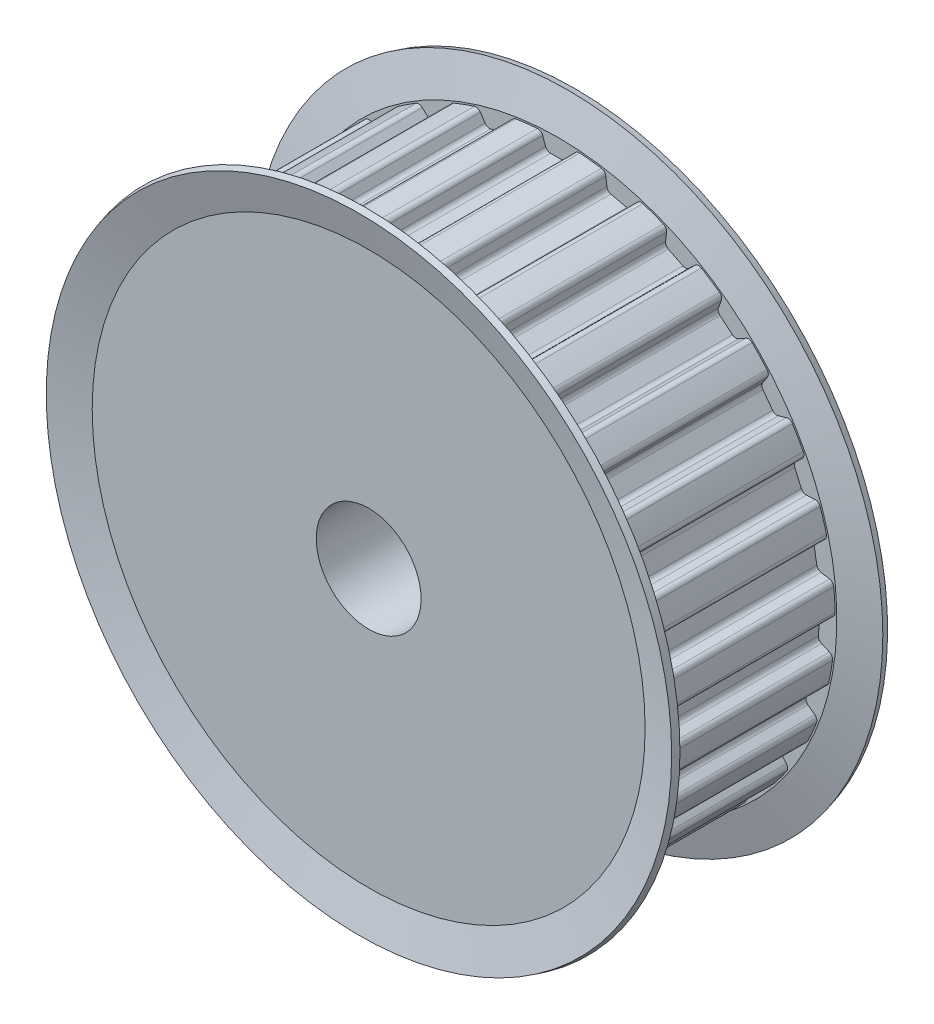
SolidWorks part; units mm, degrees
ref_plane "Front" through (0, 0, 0) normal (0, 0, 1) x (1, 0, 0)
ref_plane "Top" through (0, 0, 0) normal (0, 1, 0) x (1, 0, 0)
ref_plane "Right" through (0, 0, 0) normal (1, 0, 0) x (0, 0, -1)
sketch "support-front-body" plane through (0, 0, 0) normal (0, 0, 1) x (1, 0, 0)
  line L0 (0, 0) -> (0, 21.1) construction
  line L1 (0, 0) -> (0, -21.1) construction
  line L2 (0, 0) -> (21.1, 0) construction
  line L3 (0, 0) -> (-21.1, 0) construction
  circle A0 centre (0, 0) radius 21.1
  dimension "diam-outer" = 42.2
sketch "support-right-body" plane through (0, 0, 0) normal (1, 0, 0) x (0, 0, -1)
  line L0 (0, 0) -> (15, 0) construction
  line L1 (0, 21.1) -> (15, 21.1)
  line L2 (0, 21.1) -> (0, -21.1)
  line L3 (0, -21.1) -> (15, -21.1)
  line L4 (15, 21.1) -> (15, -21.1)
  dimension "width" = 15
sketch "support-right-hub" plane through (0, 0, 0) normal (1, 0, 0) x (0, 0, -1)
  line L0 (21, 0) -> (15, 0) construction
  line L1 (15, 15) -> (21, 15)
  line L2 (15, 15) -> (15, -15)
  line L3 (15, -15) -> (21, -15)
  line L4 (21, 15) -> (21, -15)
  line L5 (15, 21.1) -> (15, -21.1) construction
  line L6 (0, 0) -> (15, 0) construction
  line L8 (0, 21.1) -> (0, -21.1) construction
  dimension "diam-hub" = 30
  dimension "dist-hub" = 21
sketch "support-right-bore" plane through (0, 0, 0) normal (1, 0, 0) x (0, 0, -1)
  line L0 (0, 21.1) -> (0, -21.1) construction
  line L1 (0, 4) -> (21, 4)
  line L2 (0, 4) -> (0, -4)
  line L3 (0, -4) -> (21, -4)
  line L4 (21, 15) -> (21, -15) construction
  line L5 (21, 0) -> (0, 0) construction
  line L6 (0, 0) -> (15, 0) construction
  line L7 (21, 4) -> (21, -4)
  line L8 (21, -4) -> (21, 4) construction
  dimension "diam-bore" = 8
sketch "support-stop-screw-hole" plane through (0, 0, 0) normal (1, 0, 0) x (0, 0, -1)
  line L1 (6.5667, 11) -> (9.4333, 11)
  line L2 (6.5667, 11) -> (6.5667, -1)
  line L3 (8, -1) -> (9.4333, -1)
  line L4 (9.4333, 11) -> (9.4333, -1)
  line L5 (8, -1) -> (8, 11) construction
  line L6 (8, -1) -> (6.5667, -1)
  line L7 (0, 0) -> (8, 0) construction
  line L8 (0, 21.1) -> (0, -21.1) construction
  dimension "diam-stop-screw-hole" = 2.8665
  dimension "dist-stop-screw-hole" = 8
  dimension "depth-stop-screw-hole" = 12
  dimension "angle-stop-screw-hole" = 180
  dimension "height-stop-screw-hole" = 11
sketch "support-front-keygroove" plane through (0, 0, 0) normal (0, 0, 1) x (1, 0, 0)
  line L0 (0, 0) -> (0, -4) construction
  line L1 (-1, 4) -> (1, 4)
  line L2 (-1, 4) -> (-1, 1.8)
  line L3 (-1, 1.8) -> (1, 1.8)
  line L4 (1, 4) -> (1, 1.8)
  line L5 (0, 0) -> (0, 4) construction
  circle A0 centre (0, 0) radius 4 construction
  dimension "width-keygroove" = 2
  dimension "dist-keygroove" = 8
  dimension "height-keygroove" = 2.2
sketch "support-front-tooth" plane through (0, 0, 0) normal (0, 0, 1) x (1, 0, 0)
  line L0 (0, 0) -> (0, 22.2373) construction
  line L1 (-1.2186, 20.7753) -> (-0.9958, 20.1632)
  line L2 (-1.6253, 22.2373) -> (1.6253, 22.2373)
  line L3 (1.6253, 22.2373) -> (1.6253, 21.0373)
  line L4 (-1.6253, 22.2373) -> (-1.6253, 21.0373)
  line L5 (-2.5, 22.2373) -> (2.5, 22.2373) construction
  line L6 (1.6253, 21.0373) -> (2.5, 22.2373) construction
  line L7 (0, 21.1) -> (0, 19.9) construction
  line L8 (0, 21.1) -> (1.6253, 21.1) construction
  line L10 (-0.6199, 19.9) -> (0.6199, 19.9)
  line L11 (1.2186, 20.7753) -> (0.9958, 20.1632)
  line L12 (-0.9958, 20.1632) -> (-0.9, 19.9) construction
  line L13 (-0.9, 19.9) -> (-0.6199, 19.9) construction
  line L14 (0.9958, 20.1632) -> (0.9, 19.9) construction
  line L15 (0.9, 19.9) -> (0.6199, 19.9) construction
  circle A0 centre (0, 0) radius 21.1 construction
  arc A1 (-0.9958, 20.1632) -> (-0.6199, 19.9) centre (-0.6199, 20.3) ccw
  arc A3 (1.6253, 21.0373) -> (1.2186, 20.7753) centre (1.5945, 20.6385) ccw
  circle A4 centre (0, 0) radius 21.1 construction
  arc A5 (-1.6253, 21.0373) -> (-1.2186, 20.7753) centre (-1.5945, 20.6385) cw
  arc A6 (0.9958, 20.1632) -> (0.6199, 19.9) centre (0.6199, 20.3) cw
  point P26 (0, 19.9)
  dimension "rad-top" = 0.4
  dimension "rad-bottom" = 0.4
  dimension "height-tooth" = 1.2
  dimension "pitch" = 5
  dimension "angle" = 40
  dimension "width-tooth-bottom" = 1.8
sketch "support-right-flange" plane through (0, 0, 0) normal (1, 0, 0) x (0, 0, -1)
  line L0 (0, 18.905) -> (0, 21.1)
  line L1 (15, 21.1) -> (15, -21.1) construction
  line L2 (0, 21.1) -> (0.5, 21.1) construction
  line L3 (0.5, 21.234) -> (-0.2412, 24)
  line L4 (-0.7412, 23.866) -> (-0.2412, 24)
  line L5 (0.5, 21.234) -> (0.5, 18.905)
  line L6 (0.5, 18.905) -> (0, 18.905)
  line L7 (7.5, 21.1) -> (7.5, 0) construction
  line L8 (0, 21.1) -> (15, 21.1) construction
  line L9 (0, 21.1) -> (-0.7412, 23.866)
  line L10 (14.5, 18.905) -> (15, 18.905)
  line L11 (14.5, 21.234) -> (14.5, 18.905)
  line L12 (15.7412, 23.866) -> (15.2412, 24)
  line L13 (14.5, 21.234) -> (15.2412, 24)
  line L14 (15, 21.1) -> (15.7412, 23.866)
  line L15 (15, 18.905) -> (15, 21.1)
  line L16 (15, 0) -> (0, 0) construction
  line L17 (15, -18.905) -> (15, -21.1)
  line L18 (15, -21.1) -> (15.7412, -23.866)
  line L19 (14.5, -21.234) -> (15.2412, -24)
  line L20 (15.7412, -23.866) -> (15.2412, -24)
  line L21 (14.5, -21.234) -> (14.5, -18.905)
  line L22 (14.5, -18.905) -> (15, -18.905)
  line L23 (0.5, -18.905) -> (0, -18.905)
  line L24 (0.5, -21.234) -> (0.5, -18.905)
  line L25 (-0.7412, -23.866) -> (-0.2412, -24)
  line L26 (0.5, -21.234) -> (-0.2412, -24)
  line L27 (0, -21.1) -> (-0.7412, -23.866)
  line L28 (0, -18.905) -> (0, -21.1)
  line L29 (0, 0) -> (15, 0) construction
  line L30 (0, 21.1) -> (0.5, 21.234) construction
  line L31 (0.25, 18.905) -> (0.25, 20.0025) construction
  line L32 (0.25, 20.0025) -> (0.25, 21.1) construction
  line L33 (-0.4912, 23.933) -> (0.25, 21.167) construction
  line L34 (0, 21.1) -> (15, 21.1) construction
  line L35 (0, 21.1) -> (0, -21.1) construction
  dimension "angle-flange" = 15
  dimension "thickness-flange" = 0.5
  dimension "diam-flange-inner" = 37.81
  dimension "diam-flange-outer" = 48
  dimension "diam-flange-angle" = 42.2
ref_axis "ref-axis-center" through (0, 0, -15) along (0, 0, 1)
ref_plane "ref-plane-front" through (0, 0, 0) normal (0, 0, 1) x (1, 0, 0)
ref_plane "ref-plane-back" through (0, 0, -15) normal (0, 0, 1) x (1, 0, 0)
ref_plane "ref-plane-hub-front" through (0, 0, -15) normal (0, 0, 1) x (1, 0, 0)
ref_plane "ref-plane-hub-back" through (0, 0, -21) normal (0, 0, 1) x (1, 0, 0)
ref_plane "ref-plane-bore-front" through (0, 0, 0) normal (0, 0, 1) x (1, 0, 0)
ref_plane "ref-plane-bore-back" through (0, 0, -21) normal (0, 0, 1) x (1, 0, 0)
ref_plane "ref-plane-stop-screw-hole-top" through (0, 11, 0) normal (0, 1, 0) x (-1, 0, 0)
ref_axis "ref-axis-stop-screw-hole" through (0, 11, -8) along (0, -1, 0)
sketch "Sketch5" plane through (0, 0, 0) normal (1, 0, 0) x (0, 0, -1)
  line L0 (15, 21.1) -> (15, -21.1) construction
  line L1 (0, 21.1) -> (15, 21.1) construction
  line L2 (0, 21.1) -> (0, -21.1) construction
  line L3 (0, 0) -> (15, 0) construction
  line L4 (15, 21.1) -> (15, 0)
  line L5 (0, 21.1) -> (15, 21.1)
  line L6 (0, 21.1) -> (0, 0)
  line L7 (0, 0) -> (15, 0) construction
  line L8 (0, 0) -> (15, 0)
revolve "body" add sketch "Sketch5" angle 360 about L7
sketch "Sketch16" plane through (0, 0, 0) normal (1, 0, 0) x (0, 0, -1)
  line L0 (21, 15) -> (21, -15) construction
  line L1 (15, 15) -> (21, 15) construction
  line L2 (21, 0) -> (15, 0) construction
  line L3 (15, 15) -> (15, -15) construction
  line L4 (21, 15) -> (21, 0)
  line L5 (15, 15) -> (21, 15)
  line L6 (21, 0) -> (15, 0) construction
  line L7 (15, 15) -> (15, 0)
  line L8 (21, 0) -> (15, 0)
revolve "body-hub" add sketch "Sketch16" angle 360 about L6
sketch "Sketch17" plane through (0, 0, 0) normal (1, 0, 0) x (0, 0, -1)
  line L1 (21, 0) -> (0, 0) construction
  line L2 (0, 4) -> (21, 4) construction
  line L3 (0, 4) -> (0, -4) construction
  line L4 (21, 4) -> (21, -4) construction
  line L5 (21, 0) -> (0, 0) construction
  line L6 (0, 4) -> (21, 4)
  line L7 (0, 4) -> (0, 0)
  line L8 (21, 0) -> (0, 0)
  line L9 (21, 4) -> (21, 0)
revolve "body-bore" cut sketch "Sketch17" angle 360 about L5
sketch "Sketch19" plane through (0, 0, 0) normal (1, 0, 0) x (0, 0, -1)
  line L0 (6.5667, 11) -> (9.4333, 11) construction
  line L1 (8, -1) -> (8, 11) construction
  line L2 (9.4333, 11) -> (9.4333, -1) construction
  line L3 (8, -1) -> (9.4333, -1) construction
  line L4 (8, 11) -> (9.4333, 11)
  line L5 (8, -1) -> (8, 11) construction
  line L6 (9.4333, 11) -> (9.4333, -1)
  line L7 (8, -1) -> (9.4333, -1)
  line L8 (8, -1) -> (8, 11)
revolve "body-stop-screw-hole" [suppressed] cut sketch "Sketch19" angle 360 about L5
pattern_circular "pattern-stop-screw-hole" [suppressed] count 2 every 90 about axis through (0, 0, -15) along (0, 0, 1)
sketch "Sketch21" plane through (0, 0, 0) normal (0, 0, 1) x (1, 0, 0)
  line L0 (-1, 4) -> (1, 4) construction
  line L1 (-1, 4) -> (-1, 1.8) construction
  line L2 (-1, 1.8) -> (1, 1.8) construction
  line L3 (1, 4) -> (1, 1.8) construction
  line L4 (-1, 4) -> (1, 4)
  line L5 (-1, 4) -> (-1, 1.8)
  line L6 (-1, 1.8) -> (1, 1.8)
  line L7 (1, 4) -> (1, 1.8)
extrude "cut-keygroove" [suppressed] cut sketch "Sketch21" against normal up to surface (17.5 mm away)
sketch "Sketch23" plane through (0, 0, 0) normal (0, 0, 1) x (1, 0, 0)
  line L6 (1.6253, 22.2373) -> (-1.6253, 22.2373)
  line L7 (1.6253, 21.0373) -> (1.6253, 22.2373)
  line L8 (0.9958, 20.1632) -> (1.2186, 20.7753)
  line L9 (-0.6199, 19.9) -> (0.6199, 19.9)
  line L10 (-1.2186, 20.7753) -> (-0.9958, 20.1632)
  line L11 (-1.6253, 22.2373) -> (-1.6253, 21.0373)
  line L12 (1.6253, 22.2373) -> (-1.6253, 22.2373)
  line L13 (1.6253, 21.0373) -> (1.6253, 22.2373)
  line L14 (0.9958, 20.1632) -> (1.2186, 20.7753)
  line L15 (-0.6199, 19.9) -> (0.6199, 19.9)
  line L16 (-1.2186, 20.7753) -> (-0.9958, 20.1632)
  line L17 (-1.6253, 22.2373) -> (-1.6253, 21.0373)
  arc A4 (1.6253, 21.0373) -> (1.2186, 20.7753) centre (1.5945, 20.6385) ccw
  arc A5 (0.6199, 19.9) -> (0.9958, 20.1632) centre (0.6199, 20.3) ccw
  arc A6 (-0.9958, 20.1632) -> (-0.6199, 19.9) centre (-0.6199, 20.3) ccw
  arc A7 (-1.2186, 20.7753) -> (-1.6253, 21.0373) centre (-1.5945, 20.6385) ccw
  arc A8 (1.6253, 21.0373) -> (1.2186, 20.7753) centre (1.5945, 20.6385) ccw
  arc A9 (0.6199, 19.9) -> (0.9958, 20.1632) centre (0.6199, 20.3) ccw
  arc A10 (-0.9958, 20.1632) -> (-0.6199, 19.9) centre (-0.6199, 20.3) ccw
  arc A11 (-1.2186, 20.7753) -> (-1.6253, 21.0373) centre (-1.5945, 20.6385) ccw
  dimension "D1" = 0
extrude "cut-tooth" cut sketch "Sketch23" against normal up to surface (15 mm away) up to plane "ref-plane-back"
pattern_circular "pattern-tooth" count 27 over 360 about axis through (0, 0, -15) along (0, 0, 1) of "cut-tooth"
sketch "Sketch25" plane through (0, 0, 0) normal (1, 0, 0) x (0, 0, -1)
  line L0 (0, 0) -> (15, 0) construction
  line L1 (0.5, 18.905) -> (0, 18.905) construction
  line L2 (0.5, 21.234) -> (0.5, 18.905) construction
  line L4 (-0.7412, 23.866) -> (-0.2412, 24) construction
  line L5 (0, 21.1) -> (-0.7412, 23.866) construction
  line L6 (0, 18.905) -> (0, 21.1) construction
  line L7 (0, 0) -> (15, 0) construction
  line L8 (0.5, 18.905) -> (0, 18.905)
  line L9 (0.5, 21.234) -> (0.5, 18.905)
  line L10 (-0.7412, 23.866) -> (-0.2412, 24)
  line L11 (0.5, 21.234) -> (-0.2412, 24) construction
  line L12 (0, 21.1) -> (-0.7412, 23.866)
  line L13 (0, 18.905) -> (0, 21.1)
  line L14 (0.5, 21.234) -> (-0.2412, 24)
revolve "body-flange-front" add sketch "Sketch25" angle 360 about L7
sketch "Sketch26" plane through (0, 0, 0) normal (1, 0, 0) x (0, 0, -1)
  line L0 (15, 0) -> (0, 0) construction
  line L1 (14.5, 18.905) -> (15, 18.905) construction
  line L2 (14.5, 21.234) -> (14.5, 18.905) construction
  line L4 (15.7412, 23.866) -> (15.2412, 24) construction
  line L5 (15, 21.1) -> (15.7412, 23.866) construction
  line L6 (15, 18.905) -> (15, 21.1) construction
  line L7 (15, 0) -> (0, 0) construction
  line L8 (14.5, 18.905) -> (15, 18.905)
  line L9 (14.5, 21.234) -> (14.5, 18.905)
  line L10 (15.7412, 23.866) -> (15.2412, 24)
  line L11 (14.5, 21.234) -> (15.2412, 24) construction
  line L12 (15, 21.1) -> (15.7412, 23.866)
  line L13 (15, 18.905) -> (15, 21.1)
  line L14 (14.5, 21.234) -> (15.2412, 24)
revolve "body-flange-back" add sketch "Sketch26" angle 360 about L7
equation "\"diam-flange-angle@support-right-flange\" = \"diam-outer@support-front-body\""
equation "\"diam-flange-inner@support-right-flange\"=(\"diam-outer@support-front-body\" - 2 * \"height-tooth@support-front-tooth\" )  * 0.95"
